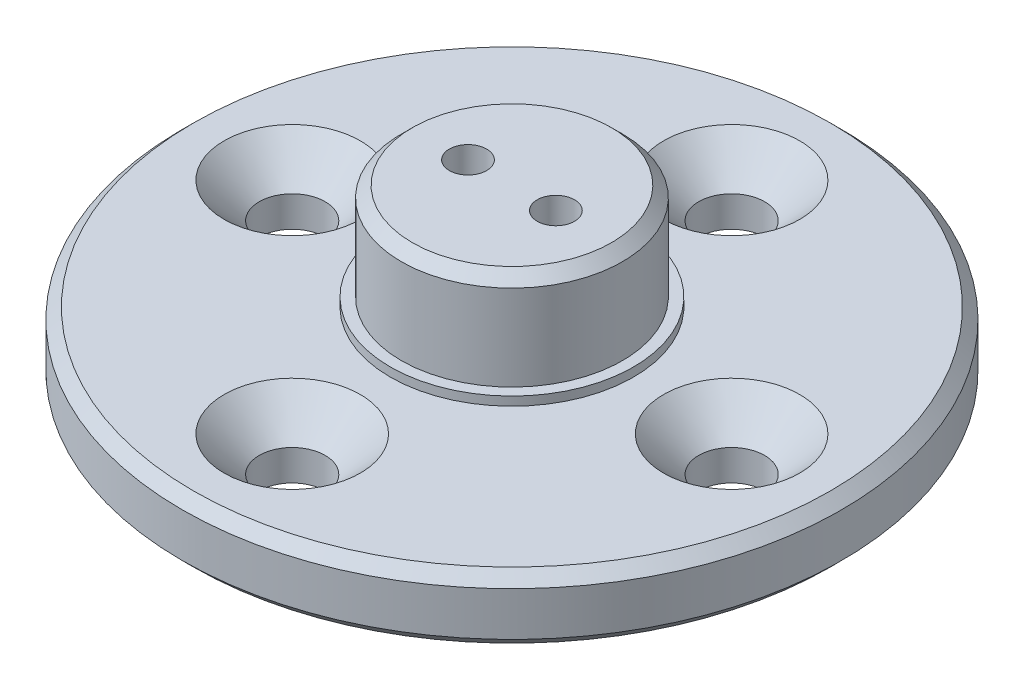
SolidWorks part; units mm, degrees
ref_plane "前视基准面" through (0, 0, 0) normal (0, 0, 1) x (1, 0, 0)
ref_plane "上视基准面" through (0, 0, 0) normal (0, 1, 0) x (1, 0, 0)
ref_plane "右视基准面" through (0, 0, 0) normal (1, 0, 0) x (0, 0, -1)
other "Configuration Table"
sketch "草图1" plane through (0, 0, 0) normal (0, 1, 0) x (1, 0, 0)
  line L0 (-21.98, 0) -> (22.6908, 0) construction
  line L1 (0, 22.7485) -> (0, -21.9381) construction
  circle A0 centre (0, 0) radius 15
  circle A1 centre (0, 10) radius 1.5
  circle A2 centre (10, 0) radius 1.5
  circle A3 centre (0, -10) radius 1.5
  circle A4 centre (-10, 0) radius 1.5
  point P15 (0, 0)
  dimension "D1" = 3
  dimension "D3" = 30
  dimension "D2" = 10
extrude "凸台-拉伸1" add sketch "草图1" along normal blind 3
sketch "草图2" plane through (0, 3, 0) normal (0, 1, 0) x (1, 0, 0)
  line L0 (0, 1.9211) -> (0, -1.7964) construction
  line L1 (-1.959, 0) -> (1.7076, 0) construction
  circle A1 centre (0, 0) radius 5.035
  circle A3 centre (2, 0) radius 0.85
  circle A4 centre (-2, 0) radius 0.85
  dimension "D1" = 10.07
  dimension "D2" = 1.7
  dimension "D3" = 4
extrude "凸台-拉伸2" add sketch "草图2" along normal blind 4.8
sketch "草图4" plane through (0, 3, 0) normal (0, 1, 0) x (1, 0, 0)
  circle A8 centre (0, 0) radius 5.535
  circle A9 centre (0, 0) radius 5.035 construction
  point P15 (0, 0)
  dimension "D1" = 0.5
extrude "凸台-拉伸3" add sketch "草图4" along normal blind 0.4
chamfer "倒角1" distance 0.5 angle 45 1 edges at (0, 7.8, 5.035)
chamfer "倒角3" distance 0.5 angle 45 2 edges at (0, 0, 15) (0, 3, 15)
chamfer "倒角4" distance 1.6 angle 45 4 edges at (10, 3, 1.5) (0, 3, 11.5) (-10, 3, 1.5) (0, 3, -8.5)
